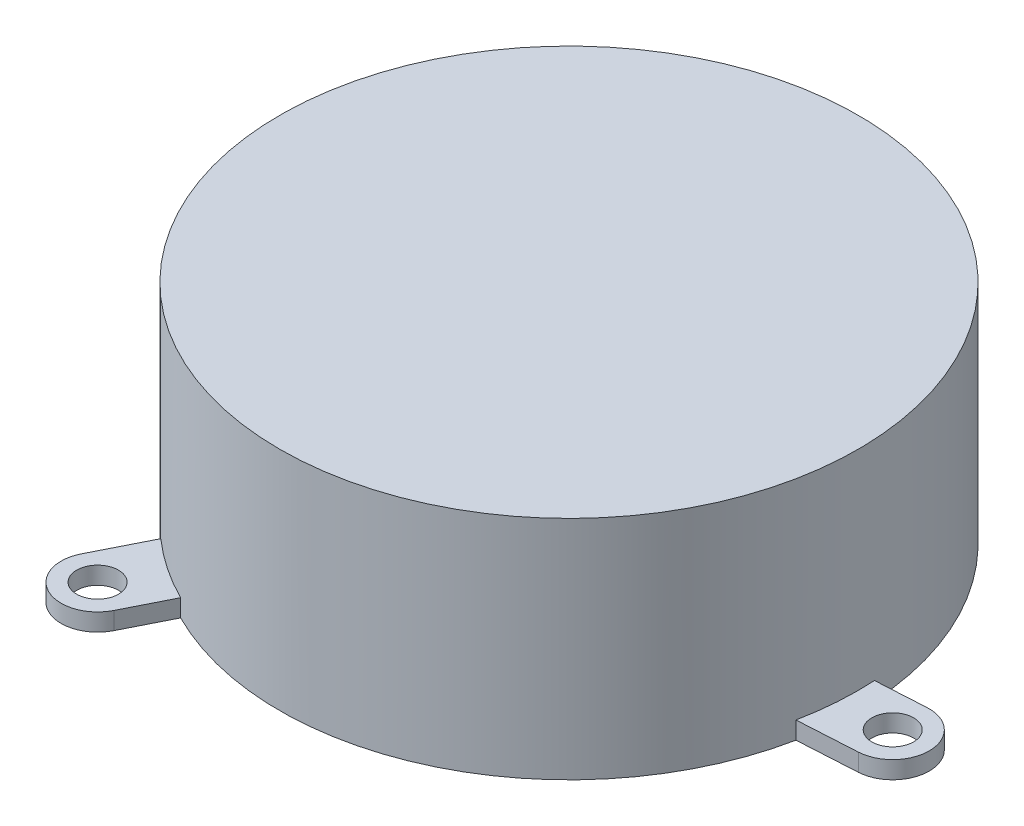
SolidWorks part; units mm, degrees
ref_plane "Front Plane" through (0, 0, 0) normal (0, 0, 1) x (1, 0, 0)
ref_plane "Top Plane" through (0, 0, 0) normal (0, 1, 0) x (1, 0, 0)
ref_plane "Right Plane" through (0, 0, 0) normal (1, 0, 0) x (0, 0, -1)
sketch "Sketch1" plane through (0, 0, 0) normal (0, 1, 0) x (1, 0, 0)
  circle A0 centre (0, 0) radius 21.463
  dimension "D1" = 42.926
extrude "Boss-Extrude1" add sketch "Sketch1" along normal blind 16.8
sketch "Sketch2" plane through (0, 0, 0) normal (0, -1, 0) x (1, 0, 0)
  line L0 (-14.1674, 16.1228) -> (-16.1374, 20.0423)
  line L1 (-11.2964, 22.4754) -> (-9.6386, 19.177)
  circle A0 centre (0, 0) radius 21.463 construction
  arc A1 (-16.1374, 20.0423) -> (-11.2964, 22.4754) centre (-13.7169, 21.2588) cw
  arc A3 (-14.1674, 16.1228) -> (-9.6386, 19.177) centre (0, 0) cw
  circle A4 centre (-13.7169, 21.2588) radius 1.55
  dimension "D2" = 3.1
extrude "Boss-Extrude2" add sketch "Sketch2" against normal blind 1.3
ref_axis "Axis1" through (0, 17.64, 0) along (0, -1, 0)
pattern_circular "CirPattern1" count 3 every 120 about axis through (0, 17.64, 0) along (0, -1, 0) of "Boss-Extrude2"
